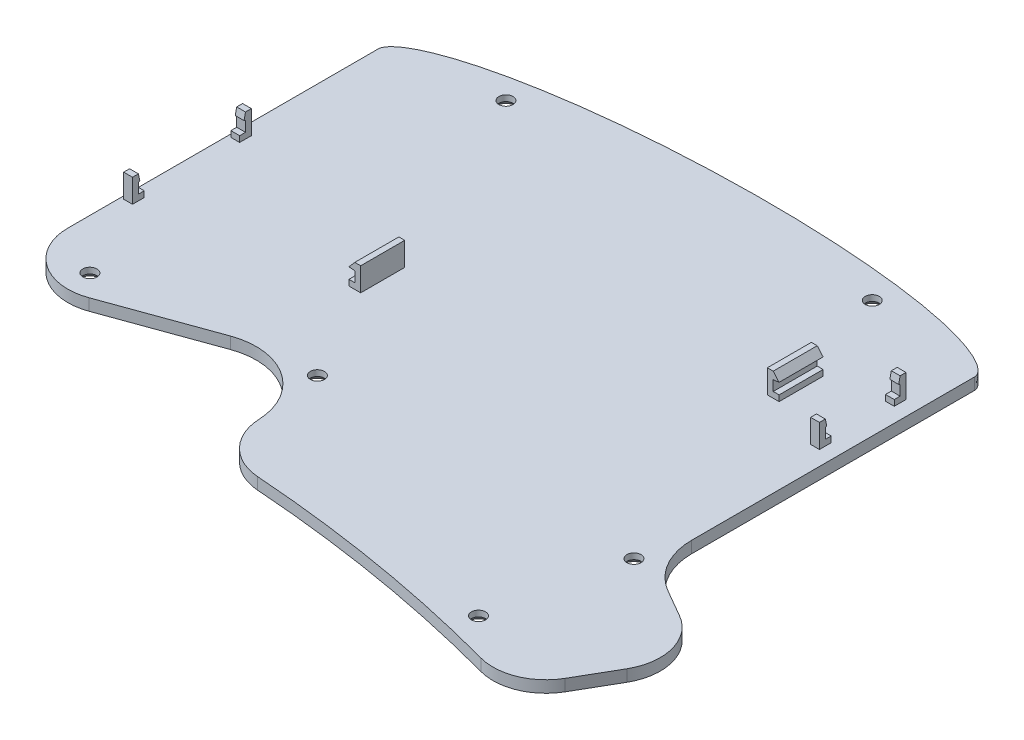
SolidWorks part; units mm, degrees
ref_plane "Front Plane" through (0, 0, 0) normal (0, 0, 1) x (1, 0, 0)
ref_plane "Top Plane" through (0, 0, 0) normal (0, 1, 0) x (1, 0, 0)
ref_plane "Right Plane" through (0, 0, 0) normal (1, 0, 0) x (0, 0, -1)
ref_plane "Plane1" through (0, -18, 0) normal (0, -1, 0) x (-1, 0, 0)
sketch "Sketch1" plane through (0, -18, 0) normal (0, -1, 0) x (-1, 0, 0)
  line L0 (3.5375, 46.5187) -> (2.5375, 46.5187) construction
  line L1 (2.5375, 46.5187) -> (2.5375, 21.3832) construction
  line L2 (-2.9636, 11.8563) -> (-7.606, 9.1767) construction
  line L3 (-10.9016, -3.1172) -> (-7.0614, -9.7705) construction
  line L4 (71.9636, 12.2185) -> (89.6698, 5.8152) construction
  line L5 (101.7306, 14.2787) -> (101.7306, 22.9312) construction
  line L6 (101.7306, 22.9312) -> (100.7306, 22.9312) construction
  line L7 (100.7306, 22.9312) -> (100.7306, 14.2787) construction
  line L8 (87.6444, 7.611) -> (72.3037, 13.1589) construction
  line L9 (-6.1953, -9.2706) -> (-10.0355, -2.6173) construction
  line L10 (-7.1061, 8.3106) -> (-2.4637, 10.9902) construction
  line L11 (3.5375, 21.3832) -> (3.5375, 46.5187) construction
  line L19 (2.5375, 69.5982) -> (2.5375, 59.5187) construction
  line L21 (2.5375, 59.5187) -> (3.5375, 59.5187) construction
  line L22 (3.5375, 59.5187) -> (3.5375, 69.5723) construction
  line L23 (100.7306, 67.1646) -> (100.7306, 43.9312) construction
  line L34 (100.7306, 43.9312) -> (101.7306, 43.9312) construction
  line L35 (101.7306, 43.9312) -> (101.7306, 67.1387) construction
  line L48 (3.5375, 46.5187) -> (2.5375, 46.5187)
  line L65 (2.5375, 46.5187) -> (2.5375, 21.3832)
  line L66 (-2.9636, 11.8563) -> (-7.606, 9.1767)
  line L67 (-10.9016, -3.1172) -> (-7.0614, -9.7705)
  line L74 (71.9636, 12.2185) -> (89.6698, 5.8152)
  line L75 (101.7306, 14.2787) -> (101.7306, 22.9312)
  line L76 (101.7306, 22.9312) -> (100.7306, 22.9312)
  line L77 (100.7306, 22.9312) -> (100.7306, 14.2787)
  line L78 (87.6444, 7.611) -> (72.3037, 13.1589)
  line L79 (-6.1953, -9.2706) -> (-10.0355, -2.6173)
  line L80 (-7.1061, 8.3106) -> (-2.4637, 10.9902)
  line L81 (3.5375, 21.3832) -> (3.5375, 46.5187)
  line L82 (2.5375, 69.5982) -> (2.5375, 59.5187)
  line L83 (2.5375, 59.5187) -> (3.5375, 59.5187)
  line L84 (3.5375, 59.5187) -> (3.5375, 69.5723)
  line L85 (100.7306, 67.1646) -> (100.7306, 43.9312)
  line L86 (100.7306, 43.9312) -> (101.7306, 43.9312)
  line L87 (101.7306, 43.9312) -> (101.7306, 67.1387)
  line L89 (2.5375, 59.5187) -> (3.5375, 59.5187)
  line L90 (2.5375, 59.5187) -> (2.5375, 46.5187)
  line L91 (2.5375, 46.5187) -> (3.5375, 46.5187)
  line L92 (3.5375, 59.5187) -> (3.5375, 46.5187)
  line L93 (100.7306, 43.9312) -> (101.7306, 43.9312)
  line L94 (100.7306, 43.9312) -> (100.7306, 22.9312)
  line L95 (100.7306, 22.9312) -> (101.7306, 22.9312)
  line L96 (101.7306, 43.9312) -> (101.7306, 22.9312)
  arc A0 (-2.9636, 11.8563) -> (2.5375, 21.3832) centre (-8.4625, 21.3832) ccw construction
  arc A1 (-7.606, 9.1767) -> (-10.9016, -3.1172) centre (-3.1069, 1.3819) ccw construction
  arc A2 (-7.0614, -9.7705) -> (3.0818, -13.9595) centre (0.7334, -5.2713) ccw construction
  arc A3 (48.8818, -6.2135) -> (3.0818, -13.9595) centre (66.0135, -246.7815) ccw construction
  arc A4 (48.8818, -6.2135) -> (57.2336, 2.3634) centre (48.2425, 2.7638) ccw construction
  arc A5 (71.9636, 12.2185) -> (57.2336, 2.3634) centre (68.2227, 1.8741) ccw construction
  arc A6 (89.6698, 5.8152) -> (101.7306, 14.2787) centre (92.7306, 14.2787) ccw construction
  arc A7 (99.5118, 10.0342) -> (100.7306, 14.2787) centre (92.7306, 14.2787) ccw construction
  arc A8 (96.3492, 10.47) -> (99.5118, 10.0342) centre (98.0284, 10.9627) ccw construction
  arc A9 (96.3492, 10.47) -> (89.9864, 9.3612) centre (93.2306, 9.5551) ccw construction
  arc A10 (87.6444, 7.611) -> (89.9864, 9.3612) centre (88.2395, 9.2567) ccw construction
  arc A11 (72.3037, 13.1589) -> (64.2101, 13.1834) centre (68.2227, 1.8741) ccw construction
  arc A12 (61.9119, 14.4747) -> (64.2101, 13.1834) centre (63.6249, 14.8326) ccw construction
  arc A13 (61.9119, 14.4747) -> (57.3666, 10.86) centre (58.7306, 13.8099) ccw construction
  arc A21 (58.1073, 8.3301) -> (57.3666, 10.86) centre (56.6322, 9.2716) ccw construction
  arc A22 (58.1073, 8.3301) -> (56.2346, 2.4079) centre (68.2227, 1.8741) ccw construction
  arc A23 (48.8107, -5.216) -> (56.2346, 2.4079) centre (48.2425, 2.7638) ccw construction
  arc A24 (48.8107, -5.216) -> (14.89, -10.0618) centre (66.0135, -246.7815) ccw construction
  arc A25 (12.7765, -8.2075) -> (14.89, -10.0618) centre (14.5206, -8.3513) ccw construction
  arc A26 (12.7765, -8.2075) -> (6.7611, -9.6299) centre (9.5375, -7.9406) ccw construction
  arc A27 (5.7019, -12.2344) -> (6.7611, -9.6299) centre (5.2661, -10.5396) ccw construction
  arc A42 (5.7019, -12.2344) -> (2.8209, -12.9942) centre (66.0135, -246.7815) ccw construction
  arc A43 (-6.1953, -9.2706) -> (2.8209, -12.9942) centre (0.7334, -5.2713) ccw construction
  arc A73 (-7.1061, 8.3106) -> (-10.0355, -2.6173) centre (-3.1069, 1.3819) ccw construction
  arc A74 (-2.4637, 10.9902) -> (-0.5914, 12.3252) centre (-8.4625, 21.3832) ccw construction
  arc A75 (2.0198, 11.964) -> (-0.5914, 12.3252) centre (0.5564, 11.0043) ccw construction
  arc A76 (2.0198, 11.964) -> (4.928, 16.9907) centre (4.7375, 13.7463) ccw construction
  arc A77 (3.3133, 19.0744) -> (4.928, 16.9907) centre (5.0306, 18.7377) ccw construction
  arc A88 (3.3133, 19.0744) -> (3.5375, 21.3832) centre (-8.4625, 21.3832) ccw construction
  arc A90 (19.327, 72.6447) -> (17.2987, 74.6407) centre (17.5982, 72.9165) ccw construction
  arc A91 (19.327, 72.6447) -> (25.5115, 73.4505) centre (22.5375, 72.1398) ccw construction
  arc A92 (26.9481, 75.8985) -> (25.5115, 73.4505) centre (27.1128, 74.1563) ccw construction
  arc A93 (80.3395, 71.9158) -> (79.0483, 74.4448) centre (78.7827, 72.7151) ccw construction
  arc A94 (80.3395, 71.9158) -> (86.4665, 70.7342) centre (83.2306, 70.4313) ccw construction
  arc A95 (88.6201, 72.5983) -> (86.4665, 70.7342) centre (88.2088, 70.8973) ccw construction
  arc A96 (-2.9636, 11.8563) -> (2.5375, 21.3832) centre (-8.4625, 21.3832) ccw
  arc A97 (-7.606, 9.1767) -> (-10.9016, -3.1172) centre (-3.1069, 1.3819) ccw
  arc A98 (-7.0614, -9.7705) -> (3.0818, -13.9595) centre (0.7334, -5.2713) ccw
  arc A99 (48.8818, -6.2135) -> (3.0818, -13.9595) centre (66.0135, -246.7815) ccw
  arc A100 (48.8818, -6.2135) -> (57.2336, 2.3634) centre (48.2425, 2.7638) ccw
  arc A101 (71.9636, 12.2185) -> (57.2336, 2.3634) centre (68.2227, 1.8741) ccw
  arc A102 (89.6698, 5.8152) -> (101.7306, 14.2787) centre (92.7306, 14.2787) ccw
  arc A103 (99.5118, 10.0342) -> (100.7306, 14.2787) centre (92.7306, 14.2787) ccw
  arc A104 (96.3492, 10.47) -> (99.5118, 10.0342) centre (98.0284, 10.9627) ccw
  arc A105 (96.3492, 10.47) -> (89.9864, 9.3612) centre (93.2306, 9.5551) ccw
  arc A106 (87.6444, 7.611) -> (89.9864, 9.3612) centre (88.2395, 9.2567) ccw
  arc A107 (72.3037, 13.1589) -> (64.2101, 13.1834) centre (68.2227, 1.8741) ccw
  arc A108 (61.9119, 14.4747) -> (64.2101, 13.1834) centre (63.6249, 14.8326) ccw
  arc A109 (61.9119, 14.4747) -> (57.3666, 10.86) centre (58.7306, 13.8099) ccw
  arc A110 (58.1073, 8.3301) -> (57.3666, 10.86) centre (56.6322, 9.2716) ccw
  arc A111 (58.1073, 8.3301) -> (56.2346, 2.4079) centre (68.2227, 1.8741) ccw
  arc A112 (48.8107, -5.216) -> (56.2346, 2.4079) centre (48.2425, 2.7638) ccw
  arc A113 (48.8107, -5.216) -> (14.89, -10.0618) centre (66.0135, -246.7815) ccw
  arc A114 (12.7765, -8.2075) -> (14.89, -10.0618) centre (14.5206, -8.3513) ccw
  arc A115 (12.7765, -8.2075) -> (6.7611, -9.6299) centre (9.5375, -7.9406) ccw
  arc A116 (5.7019, -12.2344) -> (6.7611, -9.6299) centre (5.2661, -10.5396) ccw
  arc A117 (5.7019, -12.2344) -> (2.8209, -12.9942) centre (66.0135, -246.7815) ccw
  arc A118 (-6.1953, -9.2706) -> (2.8209, -12.9942) centre (0.7334, -5.2713) ccw
  arc A119 (-7.1061, 8.3106) -> (-10.0355, -2.6173) centre (-3.1069, 1.3819) ccw
  arc A120 (-2.4637, 10.9902) -> (-0.5914, 12.3252) centre (-8.4625, 21.3832) ccw
  arc A121 (2.0198, 11.964) -> (-0.5914, 12.3252) centre (0.5564, 11.0043) ccw
  arc A122 (2.0198, 11.964) -> (4.928, 16.9907) centre (4.7375, 13.7463) ccw
  arc A123 (3.3133, 19.0744) -> (4.928, 16.9907) centre (5.0306, 18.7377) ccw
  arc A124 (3.3133, 19.0744) -> (3.5375, 21.3832) centre (-8.4625, 21.3832) ccw
  arc A125 (19.327, 72.6447) -> (17.2987, 74.6407) centre (17.5982, 72.9165) ccw
  arc A126 (19.327, 72.6447) -> (25.5115, 73.4505) centre (22.5375, 72.1398) ccw
  arc A127 (26.9481, 75.8985) -> (25.5115, 73.4505) centre (27.1128, 74.1563) ccw
  arc A128 (80.3395, 71.9158) -> (79.0483, 74.4448) centre (78.7827, 72.7151) ccw
  arc A129 (80.3395, 71.9158) -> (86.4665, 70.7342) centre (83.2306, 70.4313) ccw
  arc A130 (88.6201, 72.5983) -> (86.4665, 70.7342) centre (88.2088, 70.8973) ccw
  spline S0 degree 3 poles (3899.3998, -822.1903) (5.5841, 61.1512) (2.5122, 67.3283) (3.582, 69.6988) (3.5979, 69.7282) (3.6492, 69.814) (3.6882, 69.8682) (3.8132, 70.0256) (3.9052, 70.1212) (4.1943, 70.393) (4.4056, 70.5549) (5.0614, 71.0066) (5.5225, 71.259) (6.4661, 71.7207) (6.9495, 71.9279) (7.931, 72.3125) (8.4288, 72.4893) (9.926, 72.9834) (10.934, 73.2666) (12.9619, 73.7775) (13.982, 74.0045) (125.5269, 96.5124) (285.8926, -113.8109) (-486.7922, 4030.3663) knots -0.073548 -0.073548 -0.073548 -0.073548 0.000977 0.000977 0.001953 0.001953 0.003906 0.003906 0.007812 0.007812 0.015625 0.015625 0.03125 0.03125 0.046875 0.046875 0.0625 0.0625 0.09375 0.09375 0.125 0.125 3.496518 3.496518 3.496518 3.496518 only from (3.5375, 69.5723) to (17.2987, 74.6407) construction
  spline S1 degree 3 poles (-477.1083, -3877.3486) (-250.6602, -122.6192) (-109.5374, 63.4053) (31.5962, 76.3247) (35.7511, 76.55) (44.0555, 76.778) (52.3546, 76.7795) (60.6437, 76.3692) (68.9275, 75.7323) (73.0667, 75.3025) (204.4615, 56.7015) (338.8353, -112.6201) (-1939.6539, -3355.4068) knots -3.867215 -3.867215 -3.867215 -3.867215 0.25 0.25 0.375 0.375 0.5 0.625 0.625 0.75 0.75 4.596546 4.596546 4.596546 4.596546 only from (26.9481, 75.8985) to (79.0483, 74.4448) construction
  spline S2 degree 3 poles (1249.0887, 3890.4335) (-183.7081, -100.6963) (-18.8477, 99.9123) (90.5626, 72.1105) (91.5733, 71.8321) (93.5794, 71.2182) (94.5733, 70.8839) (96.0407, 70.3155) (96.5252, 70.115) (97.4808, 69.6829) (97.9521, 69.4516) (98.869, 68.9422) (99.3167, 68.665) (99.9393, 68.1841) (100.1392, 68.0129) (100.41, 67.7271) (100.4955, 67.6271) (100.6082, 67.4654) (100.6431, 67.4097) (100.6877, 67.3218) (100.7012, 67.2919) (101.4302, 65.2399) (101.7532, 57.7763) (-3890.1992, 195.7579) knots -2.45843 -2.45843 -2.45843 -2.45843 0.875 0.875 0.90625 0.90625 0.9375 0.9375 0.953125 0.953125 0.96875 0.96875 0.984375 0.984375 0.992188 0.992188 0.996094 0.996094 0.998047 0.998047 0.999023 0.999023 1.062703 1.062703 1.062703 1.062703 only from (88.6201, 72.5983) to (100.7306, 67.1646) construction
  spline S3 degree 3 poles (-3249.4703, 2247.9507) (12.2588, 13.1567) (104.5699, 58.2459) (101.6331, 67.6686) (101.5759, 67.7904) (101.3723, 68.1426) (101.1991, 68.3521) (100.8236, 68.7399) (100.6216, 68.9164) (100.2008, 69.2489) (99.9816, 69.4045) (99.306, 69.8491) (98.8369, 70.1129) (97.8772, 70.6032) (97.3882, 70.8281) (95.903, 71.4617) (94.8899, 71.8297) (92.8442, 72.5008) (91.8102, 72.8032) (88.692, 73.6407) (86.5884, 74.1082) (82.3631, 74.9308) (80.2384, 75.285) (73.8497, 76.2205) (69.5658, 76.6778) (60.9853, 77.3535) (56.684, 77.57) (48.0793, 77.7822) (43.7782, 77.778) (37.3289, 77.5895) (35.1795, 77.496) (30.8816, 77.2388) (28.7355, 77.0753) (24.4582, 76.6638) (22.3259, 76.4161) (18.0784, 75.8065) (15.963, 75.4464) (12.8106, 74.7679) (11.7634, 74.5184) (9.6792, 73.9504) (8.6409, 73.6322) (7.1217, 73.0749) (6.621, 72.8755) (5.6365, 72.4364) (5.1523, 72.1974) (4.4477, 71.7872) (4.2157, 71.6411) (3.7704, 71.3281) (3.5564, 71.1612) (3.2566, 70.8856) (3.1602, 70.7894) (2.9775, 70.585) (2.8913, 70.4766) (-2.8823, 61.8111) (40.625, 9.4767) (3976.1662, 517.5782) knots -0.277833 -0.277833 -0.277833 -0.277833 0.003906 0.003906 0.007812 0.007812 0.015625 0.015625 0.023437 0.023437 0.03125 0.03125 0.046875 0.046875 0.0625 0.0625 0.09375 0.09375 0.125 0.125 0.1875 0.1875 0.25 0.25 0.375 0.375 0.5 0.5 0.625 0.625 0.6875 0.6875 0.75 0.75 0.8125 0.8125 0.875 0.875 0.90625 0.90625 0.9375 0.9375 0.953125 0.953125 0.96875 0.96875 0.976562 0.976562 0.984375 0.984375 0.988281 0.988281 0.992187 0.992187 1.285678 1.285678 1.285678 1.285678 only from (101.7306, 67.1387) to (2.5375, 69.5982) construction
  spline S4 degree 3 poles (3.5375, 69.5723) (3.5412, 69.6062) (3.5543, 69.6375) (3.582, 69.6988) (3.5979, 69.7282) (3.6492, 69.814) (3.6882, 69.8682) (3.8132, 70.0256) (3.9052, 70.1212) (4.1943, 70.393) (4.4056, 70.5549) (5.0614, 71.0066) (5.5225, 71.259) (6.4661, 71.7207) (6.9495, 71.9279) (7.931, 72.3125) (8.4288, 72.4893) (9.926, 72.9834) (10.934, 73.2666) (12.9619, 73.7775) (13.982, 74.0045) (15.7682, 74.3649) (16.5324, 74.5076) (17.2987, 74.6407) knots 0 0 0 0 0.000977 0.000977 0.001953 0.001953 0.003906 0.003906 0.007812 0.007812 0.015625 0.015625 0.03125 0.03125 0.046875 0.046875 0.0625 0.0625 0.09375 0.09375 0.125 0.125 0.14824 0.14824 0.14824 0.14824
  spline S5 degree 3 poles (26.9481, 75.8985) (27.1112, 75.9139) (27.2744, 75.9291) (31.5962, 76.3247) (35.7511, 76.55) (44.0555, 76.778) (52.3546, 76.7795) (60.6437, 76.3692) (68.9275, 75.7323) (73.0667, 75.3025) (77.8175, 74.63) (78.433, 74.5393) (79.0483, 74.4448) knots 0.245096 0.245096 0.245096 0.245096 0.25 0.25 0.375 0.375 0.5 0.625 0.625 0.75 0.75 0.768598 0.768598 0.768598 0.768598
  spline S6 degree 3 poles (88.6201, 72.5983) (88.9293, 72.5236) (89.2381, 72.4471) (90.5626, 72.1105) (91.5733, 71.8321) (93.5794, 71.2182) (94.5733, 70.8839) (96.0407, 70.3155) (96.5252, 70.115) (97.4808, 69.6829) (97.9521, 69.4516) (98.869, 68.9422) (99.3167, 68.665) (99.9393, 68.1841) (100.1392, 68.0129) (100.41, 67.7271) (100.4955, 67.6271) (100.6082, 67.4654) (100.6431, 67.4097) (100.6877, 67.3218) (100.7012, 67.2919) (100.7233, 67.2299) (100.7342, 67.1976) (100.7306, 67.1646) knots 0.865518 0.865518 0.865518 0.865518 0.875 0.875 0.90625 0.90625 0.9375 0.9375 0.953125 0.953125 0.96875 0.96875 0.984375 0.984375 0.992188 0.992188 0.996094 0.996094 0.998047 0.998047 0.999023 0.999023 1 1 1 1
  spline S7 degree 3 poles (101.7306, 67.1387) (101.7353, 67.2751) (101.7134, 67.4109) (101.6331, 67.6686) (101.5759, 67.7904) (101.3723, 68.1426) (101.1991, 68.3521) (100.8236, 68.7399) (100.6216, 68.9164) (100.2008, 69.2489) (99.9816, 69.4045) (99.306, 69.8491) (98.8369, 70.1129) (97.8772, 70.6032) (97.3882, 70.8281) (95.903, 71.4617) (94.8899, 71.8297) (92.8442, 72.5008) (91.8102, 72.8032) (88.692, 73.6407) (86.5884, 74.1082) (82.3631, 74.9308) (80.2384, 75.285) (73.8497, 76.2205) (69.5658, 76.6778) (60.9853, 77.3535) (56.684, 77.57) (48.0793, 77.7822) (43.7782, 77.778) (37.3289, 77.5895) (35.1795, 77.496) (30.8816, 77.2388) (28.7355, 77.0753) (24.4582, 76.6638) (22.3259, 76.4161) (18.0784, 75.8065) (15.963, 75.4464) (12.8106, 74.7679) (11.7634, 74.5184) (9.6792, 73.9504) (8.6409, 73.6322) (7.1217, 73.0749) (6.621, 72.8755) (5.6365, 72.4364) (5.1523, 72.1974) (4.4477, 71.7872) (4.2157, 71.6411) (3.7704, 71.3281) (3.5564, 71.1612) (3.2566, 70.8856) (3.1602, 70.7894) (2.9775, 70.585) (2.8913, 70.4766) (2.6638, 70.1352) (2.547, 69.8765) (2.5375, 69.5982) knots 0 0 0 0 0.003906 0.003906 0.007812 0.007812 0.015625 0.015625 0.023437 0.023437 0.03125 0.03125 0.046875 0.046875 0.0625 0.0625 0.09375 0.09375 0.125 0.125 0.1875 0.1875 0.25 0.25 0.375 0.375 0.5 0.5 0.625 0.625 0.6875 0.6875 0.75 0.75 0.8125 0.8125 0.875 0.875 0.90625 0.90625 0.9375 0.9375 0.953125 0.953125 0.96875 0.96875 0.976562 0.976562 0.984375 0.984375 0.988281 0.988281 0.992187 0.992187 1 1 1 1
extrude "Boss-Extrude1" add sketch "Sketch1" along normal blind 2 contours S6 A130 A129 A128 S5 A127 A126 A125 S4 L84 L92 L81 A124 A123 A122 A121 A120 L80 A119 L79 A118 A117 A116 A115 A114 A113 A112 A111 A110 A109 A108 A107 L78 A106 A105 A104 A103 L77 L94 L85 | A123 A124 L81 L48 L65 A96 L66 A97 L67 A98 A99 A100 A101 L74 A102 L75 L76 L77 A103 A104 A105 A106 L78 A107 A108 A109 A110 A111 A112 A113 A114 A115 A116 A117 A118 L79 A119 L80 A120 A121 A122 | L87 S7 L82 L83 L84 S4 A125 A126 A127 S5 A128 A129 A130 S6 L85 L86 | L92 L83 L90 L48 | L96 L86 L94 L76 region at (-3.4084, -18, -33.951) region at (-46.8071, -18, -35.8063) region at (-3.0375, -18, -53.0187) region at (-3.0375, -18, -60.5668) region at (-101.2306, -18, -33.4312)
hole_wizard "CSK for M2 Flat Head Machine Screw2" positions "3DSketch8" profile "Sketch7" countersink size "M2" standard "ANSI Metric" end condition through all
sketch3d "3DSketch8"
  circle A0 centre (-22.5375, -18, -72.1398) radius 1.75 construction
  circle A1 centre (-83.2306, -18, -70.4313) radius 1.75 construction
  circle A2 centre (-93.2306, -18, -9.5551) radius 1.75 construction
  circle A3 centre (-58.7306, -18, -13.8099) radius 1.75 construction
  circle A4 centre (-9.5375, -18, 7.9406) radius 1.75 construction
  circle A5 centre (-4.7375, -18, -13.7463) radius 1.75 construction
  point P37 (-22.5375, -20, -72.1398)
  point P39 (-83.2306, -20, -70.4313)
  point P41 (-93.2306, -20, -9.5551)
  point P43 (-58.7306, -20, -13.8099)
  point P45 (-9.5375, -20, 7.9406)
  point P47 (-4.7375, -20, -13.7463)
  point P57 (-22.5375, -19.75, -72.1398)
  point P61 (-83.2306, -19.75, -70.4313)
  point P65 (-93.2306, -19.75, -9.5551)
  point P69 (-58.7306, -19.75, -13.8099)
  point P73 (-9.5375, -19.75, 7.9406)
  point P76 (-4.7375, -19.75, -13.7463)
  point P77 (0, 0, 0)
  point P78 (0, 0, 0)
  point P79 (0, 0, 0)
  point P80 (0, 0, 0)
  point P81 (0, 0, 0)
  point P82 (0, 0, 0)
  point P83 (0, 0, 0)
  point P84 (0, 0, 0)
sketch "Sketch7" plane through (-22.5375, -20, -72.1398) normal (1, 0, 0) x (0, 0, -1)
  line L0 (0, 0) -> (0, 2)
  line L1 (0, 2) -> (1.2, 2)
  line L2 (1.2, 2) -> (1.2, 1)
  line L3 (1.2, 1) -> (2.2, 0)
  line L5 (2.2, 0) -> (0, 0)
  line L6 (-1.2, 1) -> (-2.2, 0) construction
  line L11 (0, -6.35) -> (0, 107.95) construction
  dimension "Thru Hole Dia." = 2.4
  dimension "Thru Hole Depth" = 2
  dimension "Near C'Sink Dia." = 4.4
  dimension "Near C'Sink Angle" = 90
sketch "Sketch8" plane through (0, -18, 0) normal (0, 1, 0) x (1, 0, 0)
  line L0 (-101.2306, 24.3062) -> (-99.7306, 24.3062) construction
  line L1 (-101.2306, 23.3062) -> (-101.2306, 25.3062) construction
  line L2 (-101.2306, 25.3062) -> (-99.7306, 25.3062) construction
  line L3 (-99.7306, 23.3062) -> (-99.7306, 25.3062) construction
  line L4 (-101.2306, 23.3062) -> (-99.7306, 23.3062) construction
  line L5 (-101.2306, 43.5562) -> (-99.7306, 43.5562) construction
  line L6 (-101.2306, 42.5562) -> (-99.7306, 42.5562) construction
  line L7 (-101.2306, 43.5562) -> (-101.2306, 41.5562) construction
  line L8 (-99.7306, 43.5562) -> (-99.7306, 41.5562) construction
  line L9 (-101.2306, 41.5562) -> (-99.7306, 41.5562) construction
  line L10 (-69.2306, 29.6812) -> (-67.2306, 29.6812) construction
  line L11 (-69.2306, 37.1812) -> (-67.2306, 37.1812) construction
  line L12 (-67.2306, 29.6812) -> (-67.2306, 37.1812) construction
  line L13 (-68.2306, 29.6812) -> (-68.2306, 37.1812) construction
  line L14 (-69.2306, 29.6812) -> (-69.2306, 37.1812) construction
  line L15 (-15.5375, 49.2687) -> (-17.5375, 49.2687) construction
  line L16 (-15.5375, 56.7687) -> (-17.5375, 56.7687) construction
  line L17 (-16.5375, 56.7687) -> (-16.5375, 49.2687) construction
  line L18 (-15.5375, 56.7687) -> (-15.5375, 49.2687) construction
  line L19 (-17.5375, 56.7687) -> (-17.5375, 49.2687) construction
  line L20 (-5.0375, 59.3937) -> (-6.5375, 59.3937) construction
  line L21 (-5.0375, 58.3937) -> (-6.5375, 58.3937) construction
  line L22 (-5.0375, 60.3937) -> (-5.0375, 58.3937) construction
  line L23 (-5.0375, 60.3937) -> (-6.5375, 60.3937) construction
  line L24 (-6.5375, 60.3937) -> (-6.5375, 58.3937) construction
  line L25 (-5.0375, 45.6437) -> (-5.0375, 47.6437) construction
  line L26 (-5.0375, 46.6437) -> (-6.5375, 46.6437) construction
  line L27 (-5.0375, 45.6437) -> (-6.5375, 45.6437) construction
  line L28 (-6.5375, 45.6437) -> (-6.5375, 47.6437) construction
  line L29 (-5.0375, 47.6437) -> (-6.5375, 47.6437) construction
  line L30 (-101.2306, 24.3062) -> (-99.7306, 24.3062)
  line L31 (-101.2306, 23.3062) -> (-101.2306, 25.3062)
  line L32 (-101.2306, 25.3062) -> (-99.7306, 25.3062)
  line L33 (-99.7306, 23.3062) -> (-99.7306, 25.3062)
  line L34 (-101.2306, 23.3062) -> (-99.7306, 23.3062)
  line L35 (-101.2306, 43.5562) -> (-99.7306, 43.5562)
  line L36 (-101.2306, 42.5562) -> (-99.7306, 42.5562)
  line L37 (-101.2306, 43.5562) -> (-101.2306, 41.5562)
  line L38 (-99.7306, 43.5562) -> (-99.7306, 41.5562)
  line L39 (-101.2306, 41.5562) -> (-99.7306, 41.5562)
  line L40 (-69.2306, 29.6812) -> (-67.2306, 29.6812)
  line L41 (-69.2306, 37.1812) -> (-67.2306, 37.1812)
  line L42 (-67.2306, 29.6812) -> (-67.2306, 37.1812)
  line L43 (-68.2306, 29.6812) -> (-68.2306, 37.1812)
  line L44 (-69.2306, 29.6812) -> (-69.2306, 37.1812)
  line L45 (-15.5375, 49.2687) -> (-17.5375, 49.2687)
  line L46 (-15.5375, 56.7687) -> (-17.5375, 56.7687)
  line L47 (-16.5375, 56.7687) -> (-16.5375, 49.2687)
  line L48 (-15.5375, 56.7687) -> (-15.5375, 49.2687)
  line L49 (-17.5375, 56.7687) -> (-17.5375, 49.2687)
  line L50 (-5.0375, 59.3937) -> (-6.5375, 59.3937)
  line L51 (-5.0375, 58.3937) -> (-6.5375, 58.3937)
  line L52 (-5.0375, 60.3937) -> (-5.0375, 58.3937)
  line L53 (-5.0375, 60.3937) -> (-6.5375, 60.3937)
  line L54 (-6.5375, 60.3937) -> (-6.5375, 58.3937)
  line L55 (-5.0375, 45.6437) -> (-5.0375, 47.6437)
  line L56 (-5.0375, 46.6437) -> (-6.5375, 46.6437)
  line L57 (-5.0375, 45.6437) -> (-6.5375, 45.6437)
  line L58 (-6.5375, 45.6437) -> (-6.5375, 47.6437)
  line L59 (-5.0375, 47.6437) -> (-6.5375, 47.6437)
extrude "Boss-Extrude2" add sketch "Sketch8" along normal blind 1 contours L55 L59 L58 L56 | L50 L54 L51 L52 | L53 L54 L50 L52 | L48 L46 L47 L45 | L46 L49 L45 L47 | L58 L57 L55 L56 | L44 L40 L43 L41 | L43 L40 L42 L41 | L31 L34 L33 L30 | L30 L33 L32 L31 | L37 L39 L38 L36 | L38 L35 L37 L36 region at (-100.4806, -18, -24.8062) region at (-100.4806, -18, -23.8062) region at (-100.4806, -18, -43.0562) region at (-100.4806, -18, -42.0562) region at (-68.7306, -18, -33.4312) region at (-67.7306, -18, -33.4312) region at (-16.0375, -18, -53.0187) region at (-17.0375, -18, -53.0187) region at (-5.7875, -18, -58.8937) region at (-5.7875, -18, -59.8937) region at (-5.7875, -18, -46.1437) region at (-5.7875, -18, -47.1437)
extrude "Boss-Extrude3" add sketch "Sketch8<3>" along normal blind 3 from surface contours L46 L49 L45 L47 | L58 L57 L55 L56 | L53 L54 L50 L52 | L43 L40 L42 L41 | L31 L34 L33 L30 | L38 L35 L37 L36 region at (-100.4806, -18, -23.8062) region at (-100.4806, -18, -43.0562) region at (-67.7306, -18, -33.4312) region at (-17.0375, -18, -53.0187) region at (-5.7875, -18, -59.8937) region at (-5.7875, -18, -46.1437) starting at face at (-16.5375, -17, -53.0187)
sketch "Sketch8<3>" plane through (0, -18, 0) normal (0, 1, 0) x (1, 0, 0) same geometry as "Sketch8"
ref_plane "Plane2" through (0, 0, -53.0187) normal (0, 0, -1) x (-1, 0, 0)
ref_plane "Plane3" through (-5.7875, 0, 0) normal (1, 0, 0) x (0, 0, -1)
sketch "Sketch9" plane through (-5.7875, 0, 0) normal (1, 0, 0) x (0, 0, -1)
  line L0 (46.8937, -15.15) -> (46.6437, -15.25) construction
  line L1 (46.6437, -14) -> (46.6437, -15.25) construction
  line L2 (46.6437, -14) -> (46.8937, -15.15) construction
  line L3 (59.3937, -14) -> (59.3937, -15.25) construction
  line L4 (59.1437, -15.15) -> (59.3937, -15.25) construction
  line L5 (59.3937, -14) -> (59.1437, -15.15) construction
  line L6 (46.8937, -15.15) -> (46.6437, -15.25)
  line L7 (46.6437, -14) -> (46.6437, -15.25)
  line L8 (46.6437, -14) -> (46.8937, -15.15)
  line L9 (59.3937, -14) -> (59.3937, -15.25)
  line L10 (59.1437, -15.15) -> (59.3937, -15.25)
  line L11 (59.3937, -14) -> (59.1437, -15.15)
sketch "Sketch10" plane through (0, 0, -53.0187) normal (0, 0, -1) x (-1, 0, 0)
  line L0 (16.5375, -15.25) -> (16.5375, -14) construction
  line L1 (15.5375, -15.15) -> (16.5375, -15.25) construction
  line L2 (16.5375, -14) -> (15.5375, -15.15) construction
  line L3 (16.5375, -15.25) -> (16.5375, -14)
  line L4 (15.5375, -15.15) -> (16.5375, -15.25)
  line L5 (16.5375, -14) -> (15.5375, -15.15)
ref_plane "Plane4" through (0, 0, -33.4312) normal (0, 0, -1) x (-1, 0, 0)
ref_plane "Plane5" through (-100.4806, 0, 0) normal (-1, 0, 0) x (0, 0, 1)
sketch "Sketch11" plane through (0, 0, -33.4312) normal (0, 0, -1) x (-1, 0, 0)
  line L0 (69.2306, -15.15) -> (68.2306, -15.25) construction
  line L1 (68.2306, -15.25) -> (68.2306, -14) construction
  line L2 (68.2306, -14) -> (69.2306, -15.15) construction
  line L3 (69.2306, -15.15) -> (68.2306, -15.25)
  line L4 (68.2306, -15.25) -> (68.2306, -14)
  line L5 (68.2306, -14) -> (69.2306, -15.15)
sketch "Sketch12" plane through (-100.4806, 0, 0) normal (-1, 0, 0) x (0, 0, 1)
  line L0 (-24.5562, -15.15) -> (-24.3062, -15.25) construction
  line L1 (-24.3062, -14) -> (-24.3062, -15.25) construction
  line L2 (-24.3062, -14) -> (-24.5562, -15.15) construction
  line L3 (-42.3062, -15.15) -> (-42.5562, -15.25) construction
  line L4 (-42.5562, -14) -> (-42.3062, -15.15) construction
  line L5 (-42.5562, -14) -> (-42.5562, -15.25) construction
  line L6 (-24.5562, -15.15) -> (-24.3062, -15.25)
  line L7 (-24.3062, -14) -> (-24.3062, -15.25)
  line L8 (-24.3062, -14) -> (-24.5562, -15.15)
  line L9 (-42.3062, -15.15) -> (-42.5562, -15.25)
  line L10 (-42.5562, -14) -> (-42.3062, -15.15)
  line L11 (-42.5562, -14) -> (-42.5562, -15.25)
extrude "Boss-Extrude4" add sketch "Sketch12" along normal up to surface and the other way up to surface up to face at (-101.2306, -16.3333, -42.5562) other way up to face at (-99.7306, -16.3333, -42.5562)
extrude "Boss-Extrude5" add sketch "Sketch11" along normal up to surface and the other way up to surface contours L3 L4 L5 up to face at (-68.2306, -16.3333, -37.1812) other way up to face at (-68.2306, -16.3333, -29.6812)
extrude "Boss-Extrude6" add sketch "Sketch10" along normal up to surface and the other way up to surface up to face at (-16.5375, -16.3333, -56.7687) other way up to face at (-16.5375, -16.3333, -49.2687)
extrude "Boss-Extrude7" add sketch "Sketch9" along normal up to surface and the other way up to surface up to face at (-5.0375, -16.3333, -46.6437) other way up to face at (-6.5375, -16.3333, -46.6437)
